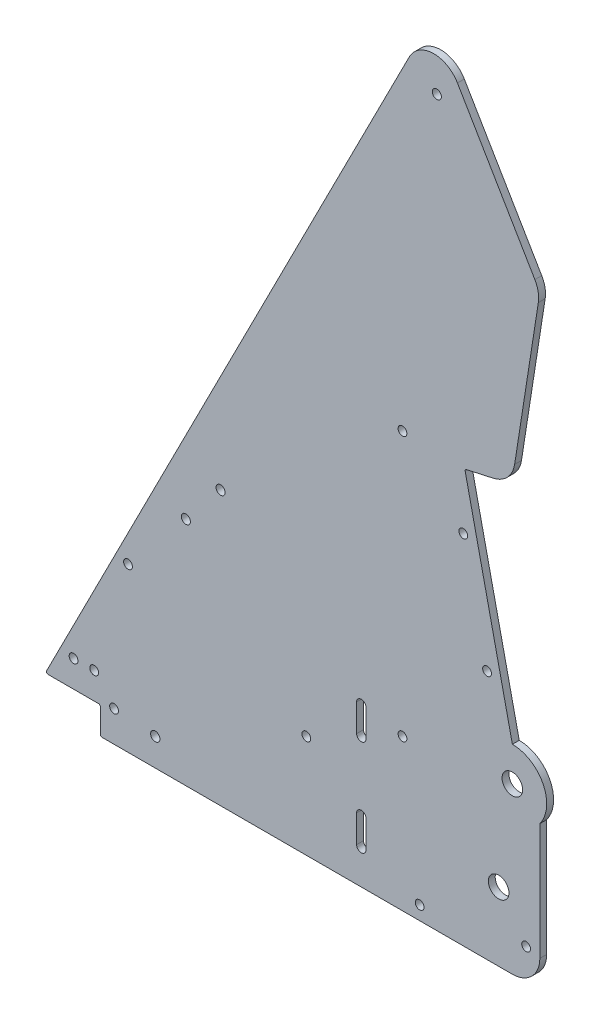
SolidWorks part; units mm, degrees
other "Markup1"
sketch "Sketch5"
ref_plane "Front Plane" through (0, 0, 0) normal (0, 0, 1) x (1, 0, 0)
ref_plane "Top Plane" through (0, 0, 0) normal (0, 1, 0) x (1, 0, 0)
ref_plane "Right Plane" through (0, 0, 0) normal (1, 0, 0) x (0, 0, -1)
sketch "Sketch1" plane through (0, 0, 0) normal (0, 0, 1) x (1, 0, 0)
  line L1 (228.6, -12.7) -> (228.6, 53.975)
  line L2 (178.7547, 351.4131) -> (0, 0)
  line L3 (228.6, 266.7) -> (178.7547, 351.4131)
  line L5 (0, 0) -> (25.4, 0)
  line L6 (25.4, 0) -> (25.4, -12.7)
  line L7 (25.4, -12.7) -> (228.6, -12.7)
  line L9 (215.9, 79.375) -> (193.9097, 178.5667)
  line L10 (193.9097, 178.5667) -> (215.6079, 183.377)
  line L11 (215.6079, 183.377) -> (228.6, 266.7)
  arc A0 (228.6, 53.975) -> (215.9, 79.375) centre (215.9, 63.5) ccw
  dimension "D7" = 12.7
  dimension "D8" = 76.2
  dimension "D10" = 31.75
  dimension "D2" = 279.4
  dimension "D3" = 25.4
  dimension "D4" = 215.9
  dimension "D5" = 394.2644
  dimension "D6" = 203.2
  dimension "D9" = 63.039
  dimension "D11" = 101.6
  dimension "D12" = 12.5
  dimension "D13" = 22.225
extrude "Boss-Extrude1" add sketch "Sketch1" along normal blind 3.175
sketch "Sketch2" plane through (0, 0, 3.175) normal (0, 0, 1) x (1, 0, 0)
  line L0 (178.7547, 351.4131) -> (0, 0) construction
  line L1 (25.4, -12.7) -> (228.6, -12.7) construction
  line L2 (215.9, 79.375) -> (193.9097, 178.5667) construction
  line L3 (193.9097, 178.5667) -> (215.6079, 183.377) construction
  line L4 (215.9, 79.375) -> (193.9097, 178.5667) construction
  line L10 (228.6, -12.7) -> (228.6, 53.975) construction
  circle A0 centre (64.9432, 94.0578) radius 2.0955
  circle A1 centre (180.975, 322.1643) radius 2.0955
  circle A2 centre (81.0071, 113.733) radius 2.0955
  circle A3 centre (193.2078, 152.3944) radius 2.032
  circle A4 centre (215.9, 63.5) radius 4.7625
  circle A7 centre (173.0375, -6.35) radius 2.032
  circle A8 centre (204.203, 102.7985) radius 2.032
  circle A26 centre (209.55, 19.05) radius 4.7625
  arc A30 (228.6, 53.975) -> (215.9, 79.375) centre (215.9, 63.5) ccw construction
  circle A31 centre (165.1, 179.3875) radius 2.032
  dimension "D3" = 4.191
  dimension "D5" = 4.191
  dimension "D9" = 4.191
  dimension "D20" = 9.525
  dimension "D23" = 9.525
  dimension "D18" = 4.064
  dimension "D26" = 4.064
  dimension "D14" = 4.064
  dimension "D2" = 15.24
  dimension "D6" = 15.24
  dimension "D7" = 25.4
  dimension "D8" = 20.6375
  dimension "D21" = 44.45
  dimension "D22" = 6.35
  dimension "D19" = 160.3375
  dimension "D24" = 44.45
  dimension "D25" = 6.35
  dimension "D27" = 25.4
  dimension "D28" = 50.8
  dimension "D29" = 6.35
  dimension "D17" = 6.35
  dimension "D33" = 55.5625
  dimension "D15" = 114.3
  dimension "D4" = 180.975
extrude "Cut-Extrude1" cut sketch "Sketch2" against normal through all
sketch "Sketch7" plane through (0, 0, 3.175) normal (0, 0, 1) x (1, 0, 0)
  line L0 (146.05, 3.175) -> (146.05, 15.875) construction
  line L1 (143.891, 3.175) -> (143.891, 15.875)
  line L2 (148.209, 3.175) -> (148.209, 15.875)
  line L3 (146.05, 47.625) -> (146.05, 60.325) construction
  line L4 (143.891, 47.625) -> (143.891, 60.325)
  line L5 (148.209, 47.625) -> (148.209, 60.325)
  line L6 (25.4, -12.7) -> (228.6, -12.7) construction
  line L12 (228.6, -12.7) -> (228.6, 53.975) construction
  line L13 (25.4, -12.7) -> (228.6, -12.7) construction
  arc A0 (143.891, 3.175) -> (148.209, 3.175) centre (146.05, 3.175) ccw
  arc A1 (148.209, 15.875) -> (143.891, 15.875) centre (146.05, 15.875) ccw
  arc A2 (143.891, 47.625) -> (148.209, 47.625) centre (146.05, 47.625) ccw
  arc A3 (148.209, 60.325) -> (143.891, 60.325) centre (146.05, 60.325) ccw
  circle A8 centre (50.8, 0) radius 2.159
  point P2 (146.05, 9.525)
  point P9 (146.05, 53.975)
  dimension "D1" = 4.318
  dimension "D5" = 4.318
  dimension "D2" = 12.7
  dimension "D3" = 12.7
  dimension "D4" = 44.45
  dimension "D6" = 95.25
  dimension "D7" = 82.55
  dimension "D8" = 15.875
  dimension "D9" = 12.7
extrude "Cut-Extrude2" cut sketch "Sketch7" against normal through all
sketch "Sketch10" plane through (0, 0, 3.175) normal (0, 0, 1) x (1, 0, 0)
  circle A1 centre (165.1, 57.15) radius 2.032
  circle A2 centre (120.65, 34.925) radius 2.032
  circle A3 centre (13.0465, 12.3347) radius 2.032
  circle A4 centre (22.5715, 12.3347) radius 2.032
  circle A5 centre (38.2114, 62.6398) radius 2.032
  point P15 (0, 0)
  point P16 (0, 0)
  dimension "D1" = 4.064
  dimension "D2" = 4.064
  dimension "D4" = 63.5
  dimension "D5" = 69.85
extrude "Cut-Extrude3" cut sketch "Sketch10" against normal up to next
fillet "Fillet1" radius 12.7 4 edges at (228.6, -12.7, 1.5875) (178.7547, 351.4131, 1.5875) (215.6079, 183.377, 1.5875) (228.6, 266.7, 1.5875)
fillet "Fillet2" radius 0.7937 4 edges at (25.4, -12.7, 1.5875) (25.4, 0, 1.5875) (193.9097, 178.5667, 1.5875) (0, 0, 1.5875)
sketch "Sketch12" plane through (0, 0, 3.175) normal (0, 0, 1) x (1, 0, 0)
  circle A0 centre (31.75, 1.5875) radius 2.032
  circle A1 centre (222.25, 1.5875) radius 2.032
  dimension "D1" = 4.064
extrude "Cut-Extrude5" cut sketch "Sketch12" against normal through all
equation "\"D6@Sketch2\"=\"D2@Sketch2\""
